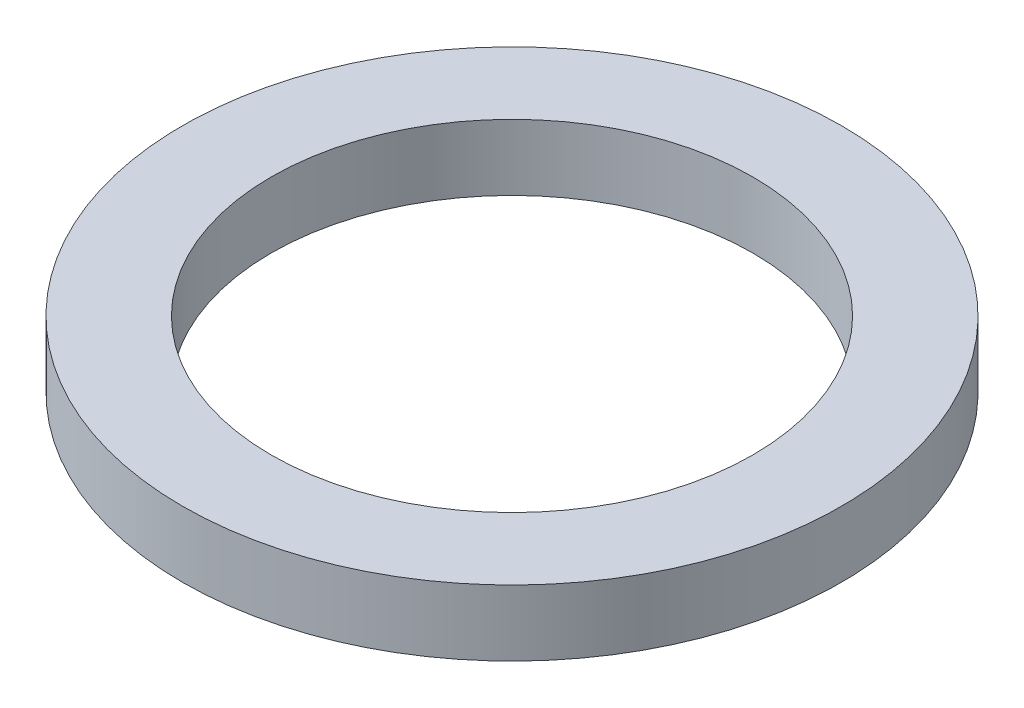
SolidWorks part; units mm, degrees
ref_plane "Front Plane" through (0, 0, 0) normal (0, 0, 1) x (1, 0, 0)
ref_plane "Top Plane" through (0, 0, 0) normal (0, 1, 0) x (1, 0, 0)
ref_plane "Right Plane" through (0, 0, 0) normal (1, 0, 0) x (0, 0, -1)
sketch "Sketch1" plane through (0, 0, 0) normal (0, 1, 0) x (1, 0, 0)
  circle A0 centre (0, 0) radius 65
  dimension "FLANGE_OD" = 130
extrude "Boss-Extrude1" add sketch "Sketch1" along normal blind 13
sketch "Sketch2" plane through (0, 0, 0) normal (0, 1, 0) x (1, 0, 0)
  circle A0 centre (0, 0) radius 47.5
  dimension "BORE_D" = 95
extrude "Cut-Extrude1" cut sketch "Sketch2" along normal through all
sketch "Sketch3" plane through (0, 13, 0) normal (0, 1, 0) x (1, 0, 0)
  circle A0 centre (0, 0) radius 28.7257 construction
  circle A1 centre (-28.7257, 0) radius 2.2761
  dimension "BOLT_D" = 4.5523
  dimension "BOLT_PCD" = 57.4513
extrude "Cut-Extrude2" cut sketch "Sketch3" against normal blind 11.0027 rebuild error yes
pattern_circular "CirPattern1" count 8 over 360 rebuild error yes
